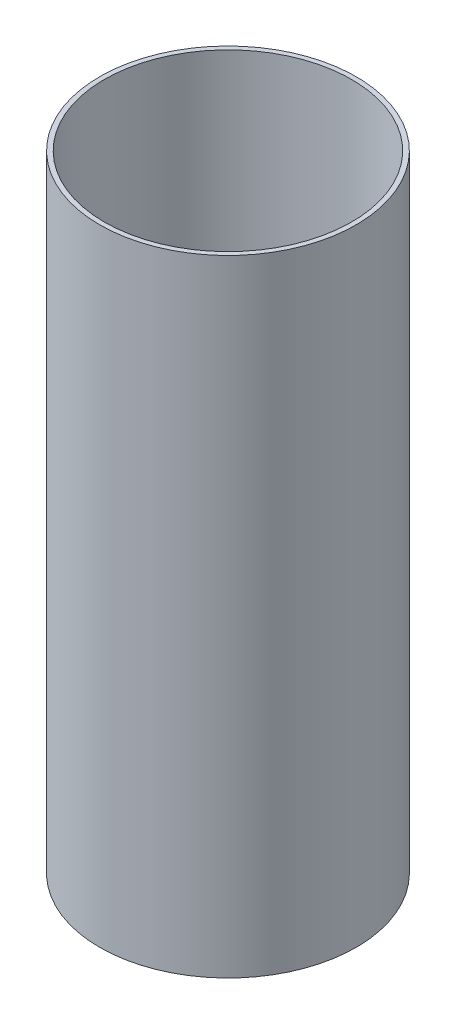
SolidWorks part; units mm, degrees
ref_plane "Front Plane" through (0, 0, 0) normal (0, 0, 1) x (1, 0, 0)
ref_plane "Top Plane" through (0, 0, 0) normal (0, 1, 0) x (1, 0, 0)
ref_plane "Right Plane" through (0, 0, 0) normal (1, 0, 0) x (0, 0, -1)
sketch "Sketch1" plane through (0, 0, 0) normal (0, 1, 0) x (1, 0, 0)
  circle A0 centre (0, 0) radius 41
  circle A1 centre (0, 0) radius 39.5
  dimension "D1" = 82
  dimension "D2" = 79
extrude "Boss-Extrude1" add sketch "Sketch1" along normal blind 200
